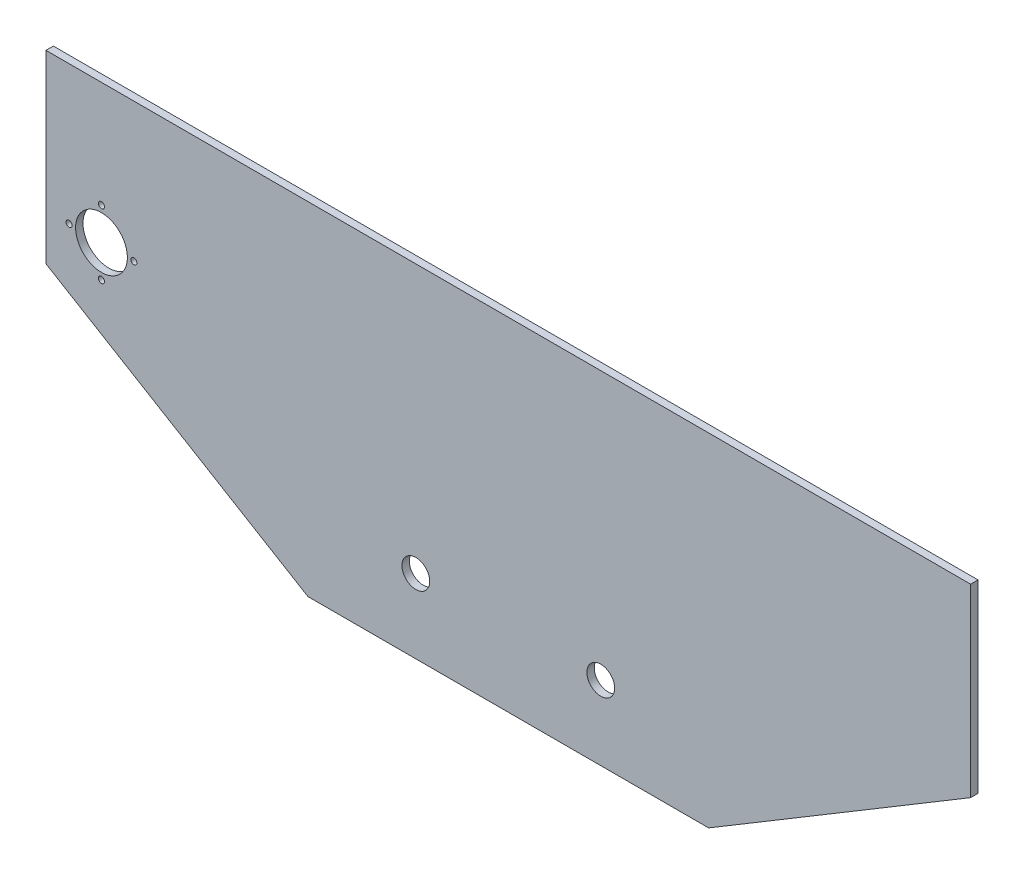
SolidWorks part; units mm, degrees
ref_plane "前视基准面" through (0, 0, 0) normal (0, 0, 1) x (1, 0, 0)
ref_plane "上视基准面" through (0, 0, 0) normal (0, 1, 0) x (1, 0, 0)
ref_plane "右视基准面" through (0, 0, 0) normal (1, 0, 0) x (0, 0, -1)
sketch "草图2" plane through (0, 0, 0) normal (0, 0, 1) x (1, 0, 0)
  line L1 (-250, -75) -> (250, -75)
  line L2 (-250, -75) -> (-250, 75)
  line L3 (-250, 75) -> (250, 75)
  line L4 (250, -75) -> (250, 75)
  line L5 (-250, -75) -> (250, 75) construction
  line L6 (-250, 75) -> (250, -75) construction
  point P0 (0, 0)
  dimension "D1" = 150
  dimension "D2" = 500
base flange "基体-法兰1" sketch "草图2" thickness 4 reverse thickness direction no parameters "D1"=0.7366
sketch "草图7" plane through (0, 0, 0) normal (0, 0, 1) x (1, 0, 0)
  line L0 (-50, 0) -> (50, 0) construction
  circle A0 centre (-50, 0) radius 7.5
  circle A1 centre (50, 0) radius 7.5
  dimension "D3" = 15
  dimension "D4" = 15
  dimension "D1" = 50
  dimension "D2" = 100
extrude "切除-拉伸1" cut sketch "草图7" against normal blind 10 normal cut yes
sketch "草图8" plane through (0, 0, 0) normal (0, 0, 1) x (1, 0, 0)
  line L0 (250, 45) -> (50, -75)
  line L1 (250, -75) -> (50, -75)
  line L2 (250, -75) -> (250, 45)
  line L9 (250, -75) -> (250, 75) construction
  line L10 (-250, -75) -> (250, -75) construction
  line L11 (0, 75) -> (0, -75) construction
  line L12 (250, 75) -> (-250, 75) construction
  line L13 (-250, -75) -> (-250, 45)
  line L14 (-250, -75) -> (-50, -75)
  line L15 (-250, 45) -> (-50, -75)
  point P2 (103.2893, -75)
  point P18 (200, 21.5975)
  dimension "D1" = 120
  dimension "D2" = 200
extrude "切除-拉伸2" cut sketch "草图8" against normal blind 10 normal cut yes
sketch "草图9" plane through (0, 0, -4) normal (0, 0, -1) x (-1, 0, 0)
  line L1 (-250, 75) -> (250, 75)
  line L2 (-250, 75) -> (-250, 145)
  line L3 (-250, 145) -> (250, 145)
  line L4 (250, 75) -> (250, 145)
  point P5 (250, 75)
  dimension "D1" = 70
extrude "凸台-拉伸1" add sketch "草图9" against normal blind 4
sketch "草图11" plane through (0, 0, -4) normal (0, 0, -1) x (-1, 0, 0)
  line L0 (-50, -75) -> (-250, 45) construction
  line L1 (-108.3333, -40) -> (185.985, -40)
  line L2 (-108.3333, -40) -> (-108.3333, -116.2069)
  line L3 (-108.3333, -116.2069) -> (185.985, -116.2069)
  line L4 (185.985, -40) -> (185.985, -116.2069)
  dimension "D1" = 40
extrude "切除-拉伸3" cut sketch "草图11" against normal blind 10 normal cut yes
sketch "草图12" plane through (0, 0, -4) normal (0, 0, -1) x (-1, 0, 0)
  circle A0 centre (220, 70) radius 14
  circle A1 centre (50, 0) radius 7.5 construction
  dimension "D1" = 28
  dimension "D2" = 170
  dimension "D3" = 70
extrude "切除-拉伸4" cut sketch "草图12" against normal blind 10 contours A0 normal cut yes
sketch "草图13" plane through (0, 0, -4) normal (0, 0, -1) x (-1, 0, 0)
  circle A0 centre (220, 87.5) radius 1.65
  circle A1 centre (220, 70) radius 14 construction
  circle A2 centre (237.5, 70) radius 1.65
  circle A3 centre (220, 52.5) radius 1.65
  circle A4 centre (202.5, 70) radius 1.65
  point P13 (220, 70)
  dimension "D2" = 3.3
  dimension "D1" = 17.5
  dimension "D3" = 4
extrude "切除-拉伸5" cut sketch "草图13" against normal blind 10 normal cut yes
sketch "折弯-线1" [suppressed] plane through (0, 0, 0) normal (0, 1, 0) x (1, 0, 0)
sketch "边界框1" [suppressed] plane through (0, 0, 0) normal (0, 1, 0) x (1, 0, 0)
sheet metal parameters "钣金2" thickness 4 parameters "D1"=0.7366
flat pattern "平板型式2" [suppressed]
sketch "折弯-线2" plane through (0, 0, 0) normal (0, 1, 0) x (1, 0, 0)
sketch3d "边界框2" [suppressed]
  line L0 (200, -100, 0) -> (-200, -100, 0) construction
  line L1 (200, 100, 0) -> (-200, 100, 0) construction
  line L2 (200, -100, 0) -> (200, 100, 0) construction
  line L3 (-200, -100, 0) -> (-200, 100, 0) construction
sheet metal parameters "钣金3" thickness 4 parameters "D1"=0.7366
flat pattern "平板型式2"
sketch "折弯-线2" plane through (0, 0, 0) normal (0, 1, 0) x (1, 0, 0)
sketch3d "边界框2" [suppressed]
  line L0 (-200, -75, 0) -> (200, -75, 0) construction
  line L1 (-200, 75, 0) -> (200, 75, 0) construction
  line L2 (-200, -75, 0) -> (-200, 75, 0) construction
  line L3 (200, -75, 0) -> (200, 75, 0) construction
sheet metal parameters "钣金4" thickness 4 parameters "D1"=0.7366
flat pattern "平板型式2"
sketch "折弯-线2" plane through (0, 0, 0) normal (0, 1, 0) x (1, 0, 0)
sketch3d "边界框2" [suppressed]
  line L0 (-200, -75, 0) -> (200, -75, 0) construction
  line L1 (-200, 75, 0) -> (200, 75, 0) construction
  line L2 (-200, -75, 0) -> (-200, 75, 0) construction
  line L3 (200, -75, 0) -> (200, 75, 0) construction
sheet metal parameters "钣金5" thickness 4 parameters "D1"=0.7366
flat pattern "平板型式2"
sketch "折弯-线2" plane through (0, 0, 0) normal (0, 1, 0) x (1, 0, 0)
sketch3d "边界框2" [suppressed]
  line L0 (-200, -75, 0) -> (200, -75, 0) construction
  line L1 (-200, 145, 0) -> (200, 145, 0) construction
  line L2 (-200, -75, 0) -> (-200, 145, 0) construction
  line L3 (200, -75, 0) -> (200, 145, 0) construction
sheet metal parameters "钣金6" thickness 4 parameters "D1"=0.7366
flat pattern "平板型式2"
sketch "折弯-线2" plane through (0, 0, 0) normal (0, 1, 0) x (1, 0, 0)
sketch3d "边界框2" [suppressed]
  line L0 (-250, -40, 0) -> (250, -40, 0) construction
  line L1 (-250, 145, 0) -> (250, 145, 0) construction
  line L2 (-250, -40, 0) -> (-250, 145, 0) construction
  line L3 (250, -40, 0) -> (250, 145, 0) construction
sheet metal parameters "钣金7" thickness 4 parameters "D1"=0.7366
flat pattern "平板型式2"
sketch "折弯-线2" plane through (0, 0, 0) normal (0, 1, 0) x (1, 0, 0)
sketch3d "边界框2" [suppressed]
  line L0 (-250, -40, 0) -> (250, -40, 0) construction
  line L1 (-250, 145, 0) -> (250, 145, 0) construction
  line L2 (-250, -40, 0) -> (-250, 145, 0) construction
  line L3 (250, -40, 0) -> (250, 145, 0) construction
sheet metal parameters "钣金8" thickness 4 parameters "D1"=0.7366
flat pattern "平板型式2"
sketch "折弯-线2" plane through (0, 0, 0) normal (0, 1, 0) x (1, 0, 0)
sketch3d "边界框2" [suppressed]
  line L0 (-250, -40, 0) -> (250, -40, 0) construction
  line L1 (-250, 145, 0) -> (250, 145, 0) construction
  line L2 (-250, -40, 0) -> (-250, 145, 0) construction
  line L3 (250, -40, 0) -> (250, 145, 0) construction
